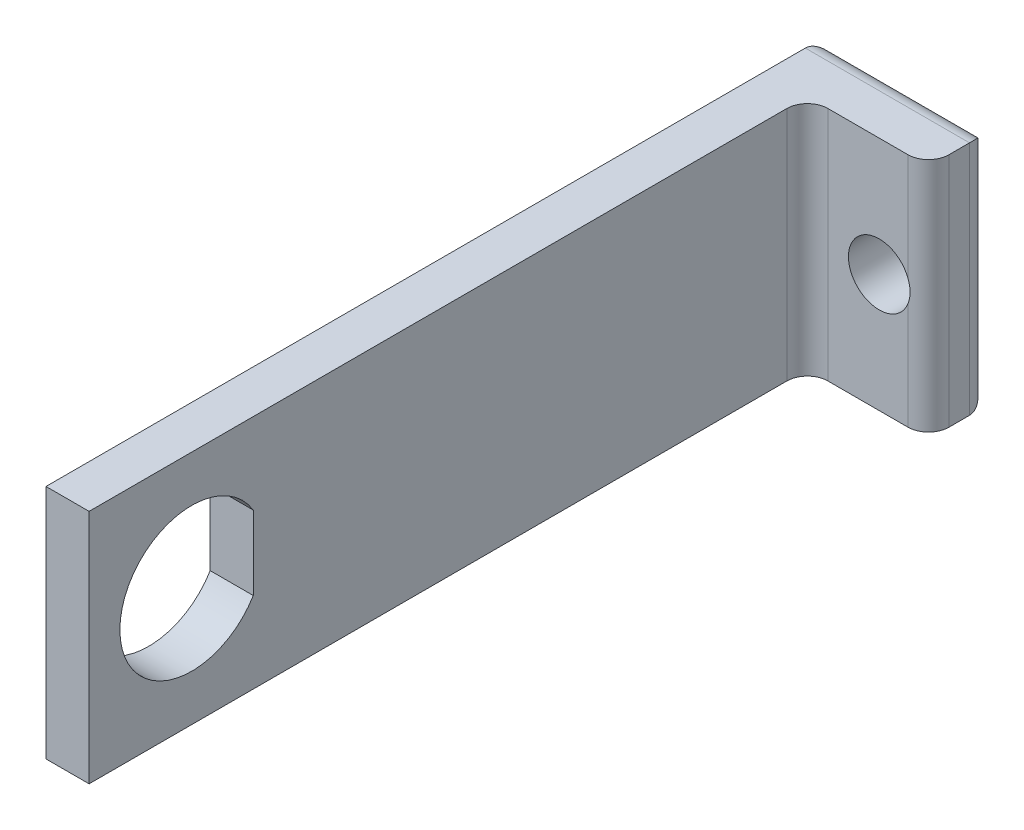
SolidWorks part; units mm, degrees
ref_plane "Front Plane" through (0, 0, 0) normal (0, 0, 1) x (1, 0, 0)
ref_plane "Top Plane" through (0, 0, 0) normal (0, 1, 0) x (1, 0, 0)
ref_plane "Right Plane" through (0, 0, 0) normal (1, 0, 0) x (0, 0, -1)
sketch "Sketch3" plane through (0, 0, 0) normal (0, 1, 0) x (1, 0, 0)
  line L0 (0, -55) -> (0, 55) construction
  line L1 (-19.5, 3) -> (-11.5, 3)
  line L24 (-19.5, 3) -> (-19.5, -35)
  line L26 (-17.4, -35) -> (-17.4, 0)
  line L31 (-17.4, 0) -> (-11.5, 0)
  line L32 (-11.5, 3) -> (-11.5, 0)
  line L33 (-19.5, -35) -> (-17.4, -35)
  dimension "D1" = 8
  dimension "D2" = 3
  dimension "D3" = 11.5
  dimension "D4" = 35
  dimension "D5" = 5.9
extrude "Boss-Extrude2" add sketch "Sketch3" along normal blind 11.5
sketch "Sketch4" plane through (0, 0, -3) normal (0, 0, -1) x (-1, 0, 0)
  line L0 (13.9, 5.75) -> (11.5, 5.75) construction
  line L1 (11.5, 11.5) -> (11.5, 0) construction
  line L2 (0, 55) -> (0, -55) construction
  circle A0 centre (13.9, 5.75) radius 1.5
  point P2 (15.2733, 5.75)
  point P6 (15.2362, 5.75)
  dimension "D1" = 3
  dimension "D2" = 13.9
extrude "Cut-Extrude1" cut sketch "Sketch4" against normal up to next
sketch "Sketch5" plane through (-19.5, 0, 0) normal (-1, 0, 0) x (0, 0, 1)
  line L0 (35, 11.5) -> (35, 0) construction
  line L1 (30, 5.75) -> (35, 5.75) construction
  line L3 (27, 3.9472) -> (27, 7.5528)
  arc A0 (27, 3.9472) -> (27, 7.5528) centre (30, 5.75) ccw
  dimension "D1" = 7
  dimension "D2" = 3
  dimension "D3" = 5
extrude "Cut-Extrude2" cut sketch "Sketch5" against normal up to next
fillet "Fillet2" radius 1 6 edges at (-19.5, 5.75, -3) (-17.4, 5.75, 0) (-11.5, 5.75, -3) (-15.5, 11.5, -3) (-15.5, 0, -3) (-11.5, 5.75, 0)
